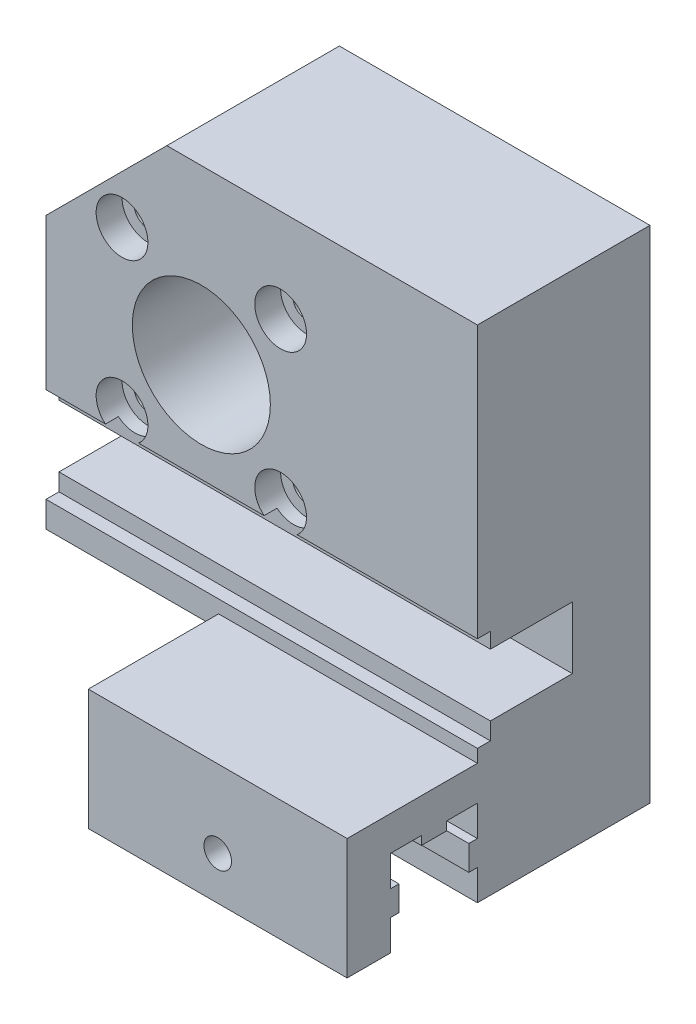
SolidWorks part; units mm, degrees
ref_plane "Front Plane" through (0, 0, 0) normal (0, 0, 1) x (1, 0, 0)
ref_plane "Top Plane" through (0, 0, 0) normal (0, 1, 0) x (1, 0, 0)
ref_plane "Right Plane" through (0, 0, 0) normal (1, 0, 0) x (0, 0, -1)
sketch "Esquisse1" plane through (0, 0, 0) normal (0, 0, 1) x (1, 0, 0)
  line L0 (25, 22.5) -> (25, -22.5)
  line L1 (-25, 22.5) -> (25, 22.5)
  line L2 (-25, 22.5) -> (-25, -22.5)
  line L3 (-25, -22.5) -> (25, -22.5)
  point P4 (-25, 0)
  point P6 (0, -22.5)
  dimension "D3" = 45
  dimension "D4" = 50
extrude "Main Extrusion" add sketch "Esquisse1" along normal blind 20
sketch "Esquisse5" plane through (0, 0, 20) normal (0, 0, 1) x (1, 0, 0)
  line L1 (-25, -22.5) -> (25, -22.5) construction
  line L3 (-25, 22.5) -> (-25, -22.5) construction
  circle A0 centre (-7, 2.5) radius 8
  dimension "D1" = 16
  dimension "D2" = 25
  dimension "D3" = 18
extrude "Gear Linear Holes" cut sketch "Esquisse5" against normal through all
sketch "Esquisse8" plane through (0, 0, 0) normal (1, 0, 0) x (0, 0, -1)
  line L0 (-20, -25.5) -> (-20, -29.05)
  line L1 (-20, -25.5) -> (-23.6, -25.5)
  line L2 (-23.6, -25.5) -> (-23.6, -26.5)
  line L3 (-23.6, -26.5) -> (-26.5, -26.5)
  line L4 (-26.5, -26.5) -> (-26.5, -25.5)
  line L5 (-35.1, -21.5) -> (0, -21.5)
  line L6 (-20, -35.5) -> (0, -35.5)
  line L7 (0, -35.5) -> (0, -21.5)
  line L8 (0, -22.5) -> (0, 22.5) construction
  line L9 (-26.5, -25.5) -> (-30.1, -25.5)
  line L10 (-20, -22.5) -> (0, -22.5) construction
  line L12 (0, 22.5) -> (0, -22.5) construction
  line L13 (-30.1, -25.5) -> (-30.1, -29.05)
  line L14 (-30.1, -35.5) -> (-35.1, -35.5)
  line L15 (-35.1, -35.5) -> (-35.1, -21.5)
  line L16 (-20, -29.05) -> (-21, -29.05)
  line L17 (-21, -29.05) -> (-21, -31.95)
  line L18 (-21, -31.95) -> (-20, -31.95)
  line L19 (-20, -31.95) -> (-20, -35.5)
  line L21 (-30.1, -29.05) -> (-29.1, -29.05)
  line L22 (-29.1, -29.05) -> (-29.1, -31.95)
  line L23 (-29.1, -31.95) -> (-30.1, -31.95)
  line L24 (-30.1, -31.95) -> (-30.1, -35.5)
  line L25 (-20, 22.5) -> (-20, -22.5) construction
  dimension "D1" = 2.9
  dimension "D2" = 10.1
  dimension "D3" = 1
  dimension "D4" = 3
  dimension "D5" = 10
  dimension "D6" = 5
  dimension "D7" = 4
extrude "Fixing Extrusion" add sketch "Esquisse8" along normal mid plane 50
sketch "Esquisse12" plane through (0, 0, 0) normal (0, 0, 1) x (1, 0, 0)
  circle A0 centre (-7, 2.5) radius 16
  dimension "D1" = 32
sketch "Esquisse13" plane through (0, 0, 20) normal (0, 0, 1) x (1, 0, 0)
  line L0 (-25, 22.5) -> (-25, -21.5) construction
  line L1 (-25, -18) -> (25, -18)
  line L2 (-25, -18) -> (-25, -10.8)
  line L3 (-25, -10.8) -> (25, -10.8)
  line L4 (25, -18) -> (25, -10.8)
  line L5 (25, -21.5) -> (25, 22.5) construction
  line L7 (-25, -21.5) -> (25, -21.5) construction
  dimension "D1" = 3.5
  dimension "D2" = 7.2
extrude "RollingBallHorizontalHole" cut sketch "Esquisse13" against normal blind 11
sketch "Esquisse14" plane through (-25, 0, 0) normal (-1, 0, 0) x (0, 0, 1)
  line L0 (0, -23) -> (20, -23)
  line L1 (0, -35.5) -> (35.1, -35.5)
  line L2 (0, -35.5) -> (0, -23)
  line L3 (20, -23) -> (20, -18)
  line L4 (35.1, -35.5) -> (35.1, -18)
  line L5 (20, -18) -> (35.1, -18)
  line L6 (20, -18) -> (20, -21.5) construction
  dimension "D1" = 12.5
extrude "FrontHole" cut sketch "Esquisse14" against normal blind 20
sketch "Esquisse15" plane through (0, 0, 35.1) normal (0, 0, 1) x (1, 0, 0)
  line L1 (25, -21.5) -> (25, -35.5) construction
  line L4 (-5, -31.95) -> (-5, -29.05) construction
  circle A1 centre (10, -30.5) radius 1.6
  point P5 (-5, -30.5)
  dimension "D1" = 3.2
  dimension "D2" = 15
extrude "BottomFixingHole" cut sketch "Esquisse15" against normal through all
extrude "ReductorMainHole" cut sketch "Esquisse12" along normal blind 5
sketch "Esquisse16" plane through (0, 0, 5) normal (0, 0, -1) x (-1, 0, 0)
  line L0 (2.6411, 11.5) -> (11.3589, 11.5)
  line L1 (2.6411, -6.5) -> (11.3589, -6.5)
  arc A0 (2.6411, 11.5) -> (2.6411, -6.5) centre (7, 2.5) ccw
  arc A2 (11.3589, 11.5) -> (11.3589, -6.5) centre (7, 2.5) cw
  circle A3 centre (7, 2.5) radius 16 construction
  dimension "D1" = 10
  dimension "D2" = 18
extrude "ReductorFrontFixingHole" cut sketch "Esquisse16" against normal blind 3
sketch "Esquisse17" plane through (0, 0, 5) normal (0, 0, -1) x (-1, 0, 0)
  line L0 (7, 2.5) -> (-2.1924, 11.6924) construction
  line L1 (19.305, 0) -> (-19.305, 0) construction
  line L2 (-2.1924, -6.6924) -> (16.1924, 11.6924) construction
  line L3 (7, 2.5) -> (16.1924, -6.6924) construction
  circle A0 centre (-2.1924, 11.6924) radius 1.6
  circle A1 centre (16.1924, 11.6924) radius 1.6
  circle A2 centre (-2.1924, -6.6924) radius 1.6
  circle A3 centre (16.1924, -6.6924) radius 1.6
  dimension "D1" = 3.2
  dimension "D2" = 45
  dimension "D3" = 13
  dimension "D4" = 13
  dimension "D5" = 13
extrude "MotorFixingHole" cut sketch "Esquisse17" against normal through all
sketch "Esquisse19" plane through (0, 0, 20) normal (0, 0, 1) x (1, 0, 0)
  circle A0 centre (-16.1924, 11.6924) radius 3
  circle A1 centre (2.1924, 11.6924) radius 3
  circle A2 centre (-16.1924, -6.6924) radius 3
  circle A3 centre (2.1924, -6.6924) radius 3
  dimension "D1" = 6
extrude "Enlèv. mat.-Extru.5" cut sketch "Esquisse19" against normal blind 3
sketch "Sketch2" plane through (25, 0, 0) normal (1, 0, 0) x (0, 0, -1)
  line L1 (-20, -20) -> (-18.5, -20)
  line L2 (-20, -20) -> (-20, -9)
  line L3 (-20, -9) -> (-18.5, -9)
  line L4 (-18.5, -20) -> (-18.5, -9)
  line L6 (-9, -18) -> (-20, -18) construction
  line L7 (-20, -10.8) -> (-20, 22.5) construction
  dimension "D1" = 11
  dimension "D2" = 1.5
  dimension "D3" = 2
extrude "CutForMakerBeamProfile" cut sketch "Sketch2" against normal through all
ref_plane "Plane1" through (0, 0, -5) normal (0, 0, 1) x (1, 0, 0)
sketch "Sketch3" plane through (0, 0, 20) normal (0, 0, 1) x (1, 0, 0)
  line L0 (-11, 22.5) -> (-25, 8.5)
  line L1 (25, 22.5) -> (-25, 22.5) construction
  line L2 (-25, 22.5) -> (-25, -9) construction
  line L3 (-25, 8.5) -> (-25, 22.5)
  line L4 (-25, 22.5) -> (-11, 22.5)
  dimension "D1" = 14
extrude "Cut-Extrude1" cut sketch "Sketch3" against normal through all
